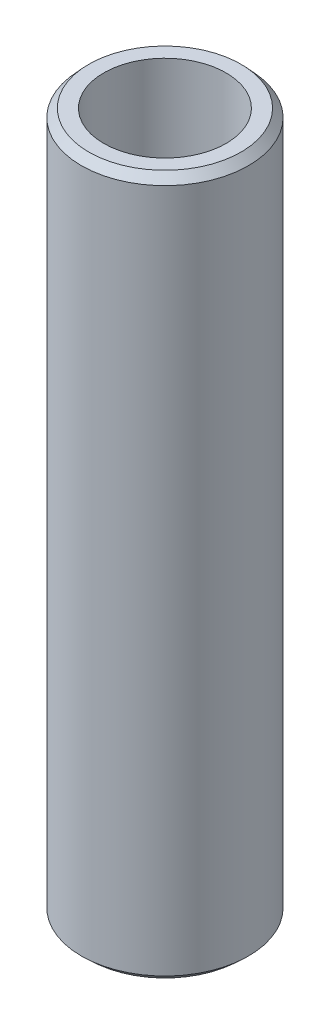
SolidWorks part; units mm, degrees
ref_plane "Front Plane" through (0, 0, 0) normal (0, 0, 1) x (1, 0, 0)
ref_plane "Top Plane" through (0, 0, 0) normal (0, 1, 0) x (1, 0, 0)
ref_plane "Right Plane" through (0, 0, 0) normal (1, 0, 0) x (0, 0, -1)
sketch "Sketch1" plane through (0, 0, 0) normal (0, 1, 0) x (1, 0, 0)
  circle A0 centre (0, 0) radius 60
  dimension "SHAFT_OD" = 120
extrude "Boss-Extrude1" add sketch "Sketch1" along normal blind 502.652
sketch "Sketch2" plane through (0, 0, 0) normal (0, 1, 0) x (1, 0, 0)
  circle A0 centre (0, 0) radius 43.9306
  dimension "BORE_D" = 87.8613
extrude "Cut-Extrude1" cut sketch "Sketch2" along normal through all
chamfer "Chamfer1" distance 5.7888 angle 42.642 2 edges at (0, 502.652, 60) (0, 0, 60) first distance on face at (0, 502.652, 60) first distance on face at (0, 0, 43.9306)
